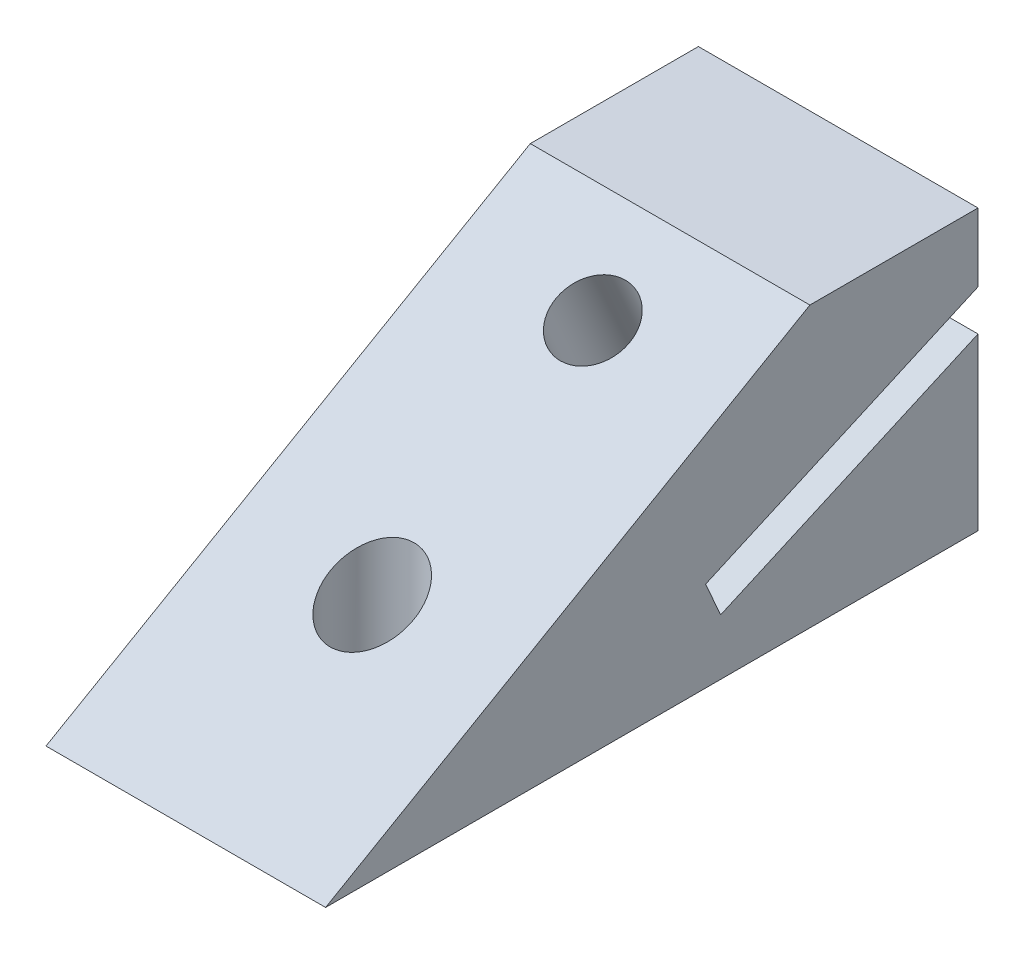
SolidWorks part; units mm, degrees
ref_plane "Front Plane" through (0, 0, 0) normal (0, 0, 1) x (1, 0, 0)
ref_plane "Top Plane" through (0, 0, 0) normal (0, 1, 0) x (1, 0, 0)
ref_plane "Right Plane" through (0, 0, 0) normal (1, 0, 0) x (0, 0, -1)
sketch "Sketch3" plane through (0, 0, 0) normal (1, 0, 0) x (0, 0, -1)
  line L0 (0, 0) -> (25.9808, 15)
  line L1 (35, 15) -> (35, 11.3349)
  line L2 (35, 0) -> (0, 0)
  line L3 (25.9808, 15) -> (35, 15)
  line L9 (20.3833, 4.8271) -> (35, 11.3349)
  line L11 (35, 9.1456) -> (21.1967, 3)
  line L12 (21.1967, 3) -> (20.3833, 4.8271)
  line L13 (35, 9.1456) -> (35, 0)
  dimension "D1" = 30
  dimension "D2" = 90
  dimension "D3" = 2
  dimension "D4" = 16
  dimension "D5" = 24
  dimension "D6" = 3
  dimension "D7" = 35
  dimension "D8" = 15
extrude "Boss-Extrude2" add sketch "Sketch3" along normal blind 15 contours L0 L1 L3 | L2 L1 region at (0, 5.914, -22.1789)
sketch "Sketch7" plane through (0, -5.3724, -2.392) normal (0, 0.9135, 0.4067) x (1, 0, 0)
  line L0 (7.5, 38.0751) -> (7.5, 22.0751)
  line L1 (15, 38.0751) -> (0, 38.0751) construction
  circle A0 centre (7.5, 25.0751) radius 2
  dimension "D2" = 4
  dimension "D1" = 16
  dimension "D3" = 3
extrude "Cut-Extrude5" cut sketch "Sketch7" along normal blind 11 and the other way blind 2 contours L0 A0 | L0 A0 region at (8.3488, 4.8265, -25.2992) region at (6.6512, 4.8265, -25.2992)
hole_wizard "M4 Clearance Hole2" positions "Sketch10" profile "Sketch11" hole size "M4" standard "ANSI Metric" end condition through all
sketch "Sketch10" plane through (-36.5, 0, -130) normal (0, -1, 0) x (0, 0, -1)
  point P0 (-120, 44)
  point P1 (-85, -33.75)
  point P2 (-85, -16)
  point P3 (-85, 1.75)
  point P4 (-120, 1.75)
  point P5 (-120, -16)
  point P6 (-120, -33.75)
  point P7 (41.8085, -45.203)
  point P9 (68.8085, -45.203)
  point P11 (68.8085, -0.7836)
  point P13 (41.8085, -0.7836)
sketch "Sketch11" plane through (7.5, 0, -10) normal (1, 0, 0) x (0, 0, -1)
  line L0 (0, 0) -> (0, 15)
  line L1 (0, 15) -> (2.25, 15)
  line L2 (2.25, 15) -> (2.25, 0)
  line L5 (2.25, 0) -> (0, 0)
  line L11 (0, -6.35) -> (0, 107.95) construction
  dimension "Thru Hole Dia." = 4.5
  dimension "Thru Hole Depth" = 15
